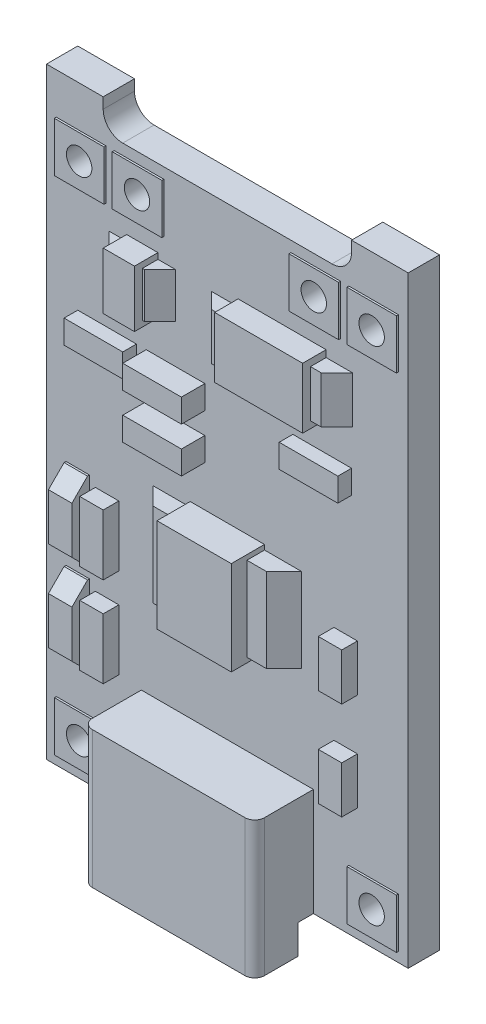
SolidWorks part; units mm, degrees
ref_plane "Přední rovina" through (0, 0, 0) normal (0, 0, 1) x (1, 0, 0)
ref_plane "Horní rovina" through (0, 0, 0) normal (0, 1, 0) x (1, 0, 0)
ref_plane "Pravá rovina" through (0, 0, 0) normal (1, 0, 0) x (0, 0, -1)
sketch "Skica1" plane through (0, 0, 0) normal (0, 0, 1) x (1, 0, 0)
  line L1 (-9.25, -15.4) -> (9.25, -15.4)
  line L2 (-9.25, -15.4) -> (-9.25, 15.4)
  line L3 (-9.25, 15.4) -> (9.25, 15.4)
  line L4 (9.25, -15.4) -> (9.25, 15.4)
  line L5 (-9.25, -15.4) -> (9.25, 15.4) construction
  line L6 (-9.25, 15.4) -> (9.25, -15.4) construction
  line L7 (6.35, 13.85) -> (-6.35, 13.85)
  line L8 (6.35, 13.85) -> (6.35, 15.4)
  line L9 (6.35, 15.4) -> (-6.35, 15.4)
  line L10 (-6.35, 13.85) -> (-6.35, 15.4)
  line L11 (6.35, 13.85) -> (-6.35, 15.4) construction
  line L12 (6.35, 15.4) -> (-6.35, 13.85) construction
  line L13 (4.4, -9.9) -> (-4.4, -9.9)
  line L14 (4.4, -9.9) -> (4.4, -16.9)
  line L15 (4.4, -16.9) -> (-4.4, -16.9)
  line L16 (-4.4, -9.9) -> (-4.4, -16.9)
  line L17 (4.4, -9.9) -> (-4.4, -16.9) construction
  line L18 (4.4, -16.9) -> (-4.4, -9.9) construction
  line L19 (-1.9, -0.3) -> (1.9, -0.3)
  line L20 (-1.9, -0.3) -> (-1.9, -5.1)
  line L21 (-1.9, -5.1) -> (1.9, -5.1)
  line L22 (1.9, -0.3) -> (1.9, -5.1)
  line L23 (-1.9, -0.3) -> (1.9, -5.1) construction
  line L24 (-1.9, -5.1) -> (1.9, -0.3) construction
  line L25 (-3.8, -0.55) -> (3.8, -0.55)
  line L26 (-3.8, -0.55) -> (-3.8, -4.85)
  line L27 (-3.8, -4.85) -> (3.8, -4.85)
  line L28 (3.8, -0.55) -> (3.8, -4.85)
  line L29 (-3.8, -0.55) -> (3.8, -4.85) construction
  line L30 (-3.8, -4.85) -> (3.8, -0.55) construction
  point P0 (0, 0)
  point P6 (0, 14.625)
  point P11 (0, -13.4)
  point P16 (0, -2.7)
  point P21 (0, -2.7)
  dimension "D1" = 18.5
  dimension "D2" = 30.8
  dimension "D3" = 8.8
  dimension "D4" = 7
  dimension "D5" = 1.5
  dimension "D6" = 12.7
  dimension "D7" = 1.55
  dimension "D8" = 3.8
  dimension "D9" = 7.6
  dimension "D10" = 4.8
  dimension "D11" = 4.3
  dimension "D12" = 15.7
extrude "Přidat vysunutím1" add sketch "Skica1" against normal blind 1.6 contours L16 L13 L14 L1 L4 L3 L8 L7 L10 L2 L25 L28 L27 L22 L21 L20 L26 L19 | L13 L16 L1 L14 | L28 L25 L22 L27 | L26 L27 L20 L25 | L20 L27 L22 L25 | L27 L20 L21 L22 | L20 L25 L22 L19 region at (0, 0.8942, 0) region at (0, -12.65, 0) region at (0, -0.425, 0) region at (0, -2.7, 0) region at (-2.85, -2.7, 0) region at (2.85, -2.7, 0) region at (0, -4.975, 0)
fillet "Zaoblit1" radius 1 2 edges at (6.35, 13.85, -0.8) (-6.35, 13.85, -0.8)
extrude "Přidat vysunutím2" add sketch "Skica1<3>" along normal blind 3 contours L13 L16 L1 L14 | L1 L16 L15 L14 region at (0, -12.65, 0) region at (0, -16.15, 0)
sketch "Skica1<3>" plane through (0, 0, 0) normal (0, 0, 1) x (1, 0, 0) same geometry as "Skica1"
extrude "Přidat vysunutím3" add sketch "Skica1<4>" along normal blind 1.7 contours L19 L22 L21 L20
sketch "Skica1<4>" plane through (0, 0, 0) normal (0, 0, 1) x (1, 0, 0) same geometry as "Skica1"
extrude "Přidat vysunutím4" add sketch "Skica1<5>" along normal blind 0.9 contours L28 L27 L26 L25
sketch "Skica1<5>" plane through (0, 0, 0) normal (0, 0, 1) x (1, 0, 0) same geometry as "Skica1"
chamfer "Zkosení1" distance 0.9 angle 45 2 edges at (-3.8, -2.7, 0.9) (3.8, -2.7, 0.9)
sketch "Skica2" plane through (0, 0, 0) normal (0, 0, 1) x (1, 0, 0)
  line L0 (6.35, 15.4) -> (9.25, 15.4) construction
  line L1 (0.55, 6.8) -> (5.05, 6.8)
  line L2 (0.55, 6.8) -> (0.55, 9.9)
  line L3 (0.55, 9.9) -> (5.05, 9.9)
  line L4 (5.05, 6.8) -> (5.05, 9.9)
  line L5 (0.55, 6.8) -> (5.05, 9.9) construction
  line L6 (0.55, 9.9) -> (5.05, 6.8) construction
  line L7 (-0.8, 7.15) -> (6.4, 7.15)
  line L8 (-0.8, 7.15) -> (-0.8, 9.55)
  line L9 (-0.8, 9.55) -> (6.4, 9.55)
  line L10 (6.4, 7.15) -> (6.4, 9.55)
  line L11 (-0.8, 7.15) -> (6.4, 9.55) construction
  line L12 (-0.8, 9.55) -> (6.4, 7.15) construction
  line L13 (-5.15, 7) -> (-3.55, 7)
  line L14 (-5.15, 7) -> (-5.15, 9.9)
  line L15 (-5.15, 9.9) -> (-3.55, 9.9)
  line L16 (-3.55, 7) -> (-3.55, 9.9)
  line L17 (-5.15, 7) -> (-3.55, 9.9) construction
  line L18 (-5.15, 9.9) -> (-3.55, 7) construction
  line L19 (-6.05, 7.3) -> (-2.65, 7.3)
  line L20 (-6.05, 7.3) -> (-6.05, 9.6)
  line L21 (-6.05, 9.6) -> (-2.65, 9.6)
  line L22 (-2.65, 7.3) -> (-2.65, 9.6)
  line L23 (-6.05, 7.3) -> (-2.65, 9.6) construction
  line L24 (-6.05, 9.6) -> (-2.65, 7.3) construction
  line L25 (-9.25, 15.4) -> (-6.35, 15.4) construction
  line L26 (9.25, -15.4) -> (9.25, 15.4) construction
  line L27 (-9.25, -15.4) -> (-9.25, 15.4) construction
  point P0 (2.8, 8.35)
  point P5 (2.8, 8.35)
  point P10 (-4.35, 8.45)
  point P15 (-4.35, 8.45)
  dimension "D1" = 2.9
  dimension "D2" = 3.1
  dimension "D3" = 4.5
  dimension "D4" = 1.6
  dimension "D5" = 3.4
  dimension "D6" = 7.2
  dimension "D7" = 2.4
  dimension "D8" = 5.5
  dimension "D9" = 5.5
  dimension "D10" = 4.2
  dimension "D11" = 4.1
  dimension "D12" = 2.3
extrude "Přidat vysunutím5" add sketch "Skica2" along normal blind 1.2 contours L15 L16 L13 L14 | L3 L4 L1 L2
extrude "Přidat vysunutím6" add sketch "Skica2<3>" along normal blind 0.8 contours L21 L22 L19 L20 | L9 L10 L7 L8
sketch "Skica2<3>" plane through (0, 0, 0) normal (0, 0, 1) x (1, 0, 0) same geometry as "Skica2"
chamfer "Zkosení2" distance 0.8 angle 45 4 edges at (6.4, 8.35, 0.8) (-0.8, 8.35, 0.8) (-2.65, 8.45, 0.8) (-6.05, 8.45, 0.8)
sketch "Skica3" plane through (0, -16.9, 0) normal (0, -1, 0) x (1, 0, 0)
  line L0 (-4, 0.4) -> (4, 0.4)
  line L1 (4, 0.4) -> (4, 2.6)
  line L2 (4, 2.6) -> (-4, 2.6)
  line L3 (-4, 2.6) -> (-4, 0.4)
  line L4 (-4.4, 0) -> (4.4, 0)
  line L5 (4.4, 0) -> (4.4, 3)
  line L6 (4.4, 3) -> (-4.4, 3)
  line L7 (-4.4, 3) -> (-4.4, 0)
  line L8 (-4.4, 0) -> (4.4, 0)
  line L9 (4.4, 0) -> (4.4, 3)
  line L10 (4.4, 3) -> (-4.4, 3)
  line L11 (-4.4, 3) -> (-4.4, 0)
  dimension "D1" = 0
  dimension "D2" = 0.4
extrude "Odebrat vysunutím1" cut sketch "Skica3" against normal blind 3.6 contours L2 L3 L0 L1 region at (0, -16.9, 1.5)
fillet "Zaoblit2" radius 1 2 edges at (-4, -15.1, 0.4) (4, -15.1, 0.4)
chamfer "Zkosení3" distance 0.8 angle 45 2 edges at (4.4, -16.15, 0) (-4.4, -16.15, 0)
fillet "Zaoblit3" radius 0.5 2 edges at (-4.4, -13.4, 3) (4.4, -13.4, 3)
sketch "Skica4" plane through (0, 0, 0) normal (0, 0, 1) x (1, 0, 0)
  line L0 (9.25, -15.4) -> (9.25, 15.4) construction
  line L1 (5.45, -4.6) -> (6.65, -4.6)
  line L2 (5.45, -4.6) -> (5.45, -2.2)
  line L3 (5.45, -2.2) -> (6.65, -2.2)
  line L4 (6.65, -4.6) -> (6.65, -2.2)
  line L5 (5.45, -9.6) -> (6.65, -9.6)
  line L6 (5.45, -9.6) -> (5.45, -7.2)
  line L7 (5.45, -7.2) -> (6.65, -7.2)
  line L8 (6.65, -9.6) -> (6.65, -7.2)
  line L9 (4.4, -15.4) -> (9.25, -15.4) construction
  dimension "D1" = 2.6
  dimension "D2" = 1.2
  dimension "D3" = 2.4
  dimension "D4" = 5.8
  dimension "D5" = 13.2
extrude "Přidat vysunutím7" add sketch "Skica4" along normal blind 0.8
sketch "Skica5" plane through (0, 0, 0) normal (0, 0, 1) x (1, 0, 0)
  line L0 (-9.25, -15.4) -> (-9.25, 15.4) construction
  line L1 (-7.65, 4.1) -> (-4.65, 4.1)
  line L2 (-7.65, 4.1) -> (-7.65, 5.3)
  line L3 (-7.65, 5.3) -> (-4.65, 5.3)
  line L4 (-4.65, 4.1) -> (-4.65, 5.3)
  line L5 (-4.15, 4.1) -> (-1.15, 4.1)
  line L6 (-4.15, 4.1) -> (-4.15, 5.3)
  line L7 (-4.15, 5.3) -> (-1.15, 5.3)
  line L8 (-1.15, 4.1) -> (-1.15, 5.3)
  line L9 (-4.15, 1.8) -> (-1.15, 1.8)
  line L10 (-4.15, 1.8) -> (-4.15, 3)
  line L11 (-4.15, 3) -> (-1.15, 3)
  line L12 (-1.15, 1.8) -> (-1.15, 3)
  line L13 (3.35, 4.1) -> (6.35, 4.1)
  line L14 (3.35, 4.1) -> (3.35, 5.3)
  line L15 (3.35, 5.3) -> (6.35, 5.3)
  line L16 (6.35, 4.1) -> (6.35, 5.3)
  line L17 (9.25, -15.4) -> (9.25, 15.4) construction
  line L18 (-9.25, 15.4) -> (-6.35, 15.4) construction
  point P20 (-6.15, 5.3)
  dimension "D1" = 1.2
  dimension "D2" = 8.1
  dimension "D3" = 5.9
  dimension "D4" = 4.6
  dimension "D5" = 3
  dimension "D6" = 10.1
  dimension "D7" = 3.5
extrude "Přidat vysunutím8" add sketch "Skica5" along normal blind 0.7 contours L3 L4 L1 L2 | L15 L16 L13 L14
extrude "Přidat vysunutím9" add sketch "Skica5<3>" along normal blind 1.2 contours L8 L7 L6 L5 | L12 L11 L10 L9
sketch "Skica5<3>" plane through (0, 0, 0) normal (0, 0, 1) x (1, 0, 0) same geometry as "Skica5"
sketch "Skica6" plane through (0, 0, 0) normal (0, 0, 1) x (1, 0, 0)
  line L0 (-9.25, -15.4) -> (-9.25, 15.4) construction
  line L1 (-8.25, -5.7) -> (-7.05, -5.7)
  line L2 (-8.25, -5.7) -> (-8.25, -1.7)
  line L3 (-8.25, -1.7) -> (-7.05, -1.7)
  line L4 (-7.05, -5.7) -> (-7.05, -1.7)
  line L5 (-8.25, -10.3) -> (-7.05, -10.3)
  line L6 (-8.25, -10.3) -> (-8.25, -6.3)
  line L7 (-8.25, -6.3) -> (-7.05, -6.3)
  line L8 (-7.05, -10.3) -> (-7.05, -6.3)
  line L9 (-6.75, -5.2) -> (-5.55, -5.2)
  line L10 (-6.75, -5.2) -> (-6.75, -2.1)
  line L11 (-6.75, -2.1) -> (-5.55, -2.1)
  line L12 (-5.55, -5.2) -> (-5.55, -2.1)
  line L13 (-6.75, -9.8) -> (-5.55, -9.8)
  line L14 (-6.75, -9.8) -> (-6.75, -6.7)
  line L15 (-6.75, -6.7) -> (-5.55, -6.7)
  line L16 (-5.55, -9.8) -> (-5.55, -6.7)
  line L17 (-9.25, -15.4) -> (-4.4, -15.4) construction
  dimension "D1" = 4
  dimension "D2" = 1.2
  dimension "D3" = 1
  dimension "D4" = 3.7
  dimension "D5" = 3.1
  dimension "D6" = 8.6
  dimension "D7" = 7.7
  dimension "D8" = 5.6
  dimension "D9" = 5.1
extrude "Přidat vysunutím10" add sketch "Skica6" along normal blind 0.8 contours L13 L16 L15 L14 | L9 L12 L11 L10
extrude "Přidat vysunutím11" add sketch "Skica6<3>" along normal blind 0.9 contours L5 L8 L7 L6 | L1 L4 L3 L2 region at (-7.65, -3.7, 0) region at (-7.65, -8.3, 0)
sketch "Skica6<3>" plane through (0, 0, 0) normal (0, 0, 1) x (1, 0, 0) same geometry as "Skica6"
chamfer "Zkosení4" distance 0.8 angle 45 4 edges at (-7.65, -1.7, 0.9) (-7.65, -5.7, 0.9) (-7.65, -6.3, 0.9) (-7.65, -10.3, 0.9)
sketch "Skica7" plane through (0, 0, 0) normal (0, 0, 1) x (1, 0, 0)
  line L0 (0, 0) -> (0, 19.3834) construction
  line L1 (-9.25, -15.4) -> (-9.25, 15.4) construction
  line L2 (-6.21, 10.76) -> (-8.75, 10.76)
  line L3 (-6.21, 10.76) -> (-6.21, 13.3)
  line L4 (-6.21, 13.3) -> (-8.75, 13.3)
  line L5 (-8.75, 10.76) -> (-8.75, 13.3)
  line L6 (-6.21, 10.76) -> (-8.75, 13.3) construction
  line L7 (-6.21, 13.3) -> (-8.75, 10.76) construction
  line L8 (-3.25, 10.76) -> (-5.79, 10.76)
  line L9 (-3.25, 10.76) -> (-3.25, 13.3)
  line L10 (-3.25, 13.3) -> (-5.79, 13.3)
  line L11 (-5.79, 10.76) -> (-5.79, 13.3)
  line L12 (-3.25, 10.76) -> (-5.79, 13.3) construction
  line L13 (-3.25, 13.3) -> (-5.79, 10.76) construction
  line L14 (-9.25, 15.4) -> (-6.35, 15.4) construction
  line L15 (-9.25, -15.4) -> (-4.4, -15.4) construction
  line L16 (-6.21, -12.36) -> (-8.75, -12.36)
  line L17 (-6.21, -12.36) -> (-6.21, -14.9)
  line L18 (-6.21, -14.9) -> (-8.75, -14.9)
  line L19 (-8.75, -12.36) -> (-8.75, -14.9)
  line L20 (-6.21, -12.36) -> (-8.75, -14.9) construction
  line L21 (-6.21, -14.9) -> (-8.75, -12.36) construction
  line L22 (6.21, -14.9) -> (8.75, -12.36) construction
  line L23 (6.21, -12.36) -> (8.75, -14.9) construction
  line L24 (3.25, 13.3) -> (5.79, 10.76) construction
  line L25 (3.25, 10.76) -> (5.79, 13.3) construction
  line L26 (6.21, 13.3) -> (8.75, 10.76) construction
  line L27 (6.21, 10.76) -> (8.75, 13.3) construction
  line L28 (8.75, -12.36) -> (8.75, -14.9)
  line L29 (6.21, -14.9) -> (8.75, -14.9)
  line L30 (6.21, -12.36) -> (6.21, -14.9)
  line L31 (6.21, -12.36) -> (8.75, -12.36)
  line L32 (5.79, 10.76) -> (5.79, 13.3)
  line L33 (3.25, 13.3) -> (5.79, 13.3)
  line L34 (3.25, 10.76) -> (3.25, 13.3)
  line L35 (3.25, 10.76) -> (5.79, 10.76)
  line L36 (8.75, 10.76) -> (8.75, 13.3)
  line L37 (6.21, 13.3) -> (8.75, 13.3)
  line L38 (6.21, 10.76) -> (6.21, 13.3)
  line L39 (6.21, 10.76) -> (8.75, 10.76)
  circle A0 centre (-7.48, 12.03) radius 0.65
  circle A1 centre (-4.52, 12.03) radius 0.65
  circle A2 centre (-7.48, -13.63) radius 0.65
  circle A3 centre (7.48, -13.63) radius 0.65
  circle A4 centre (4.52, 12.03) radius 0.65
  circle A5 centre (7.48, 12.03) radius 0.65
  point P3 (-7.48, 12.03)
  point P8 (-4.52, 12.03)
  point P17 (-7.8, 15.4)
  point P22 (-7.48, -13.63)
  dimension "D5" = 1.3
  dimension "D1" = 2.54
  dimension "D2" = 5.5
  dimension "D3" = 6
  dimension "D4" = 2.1
  dimension "D6" = 0.5
extrude "Přidat vysunutím12" add sketch "Skica7" along normal blind 0.1 and the other way blind 1.2
extrude "Odebrat vysunutím2" cut sketch "Skica7<2>" against normal through all contours A2 | A3 | A0 | A1 | A4 | A5 region at (-7.48, 12.03, 0) region at (-4.52, 12.03, 0) region at (-7.48, -13.63, 0) region at (7.48, -13.63, 0) region at (4.52, 12.03, 0) region at (7.48, 12.03, 0)
sketch "Skica7<2>" plane through (0, 0, 0) normal (0, 0, 1) x (1, 0, 0) same geometry as "Skica7"
